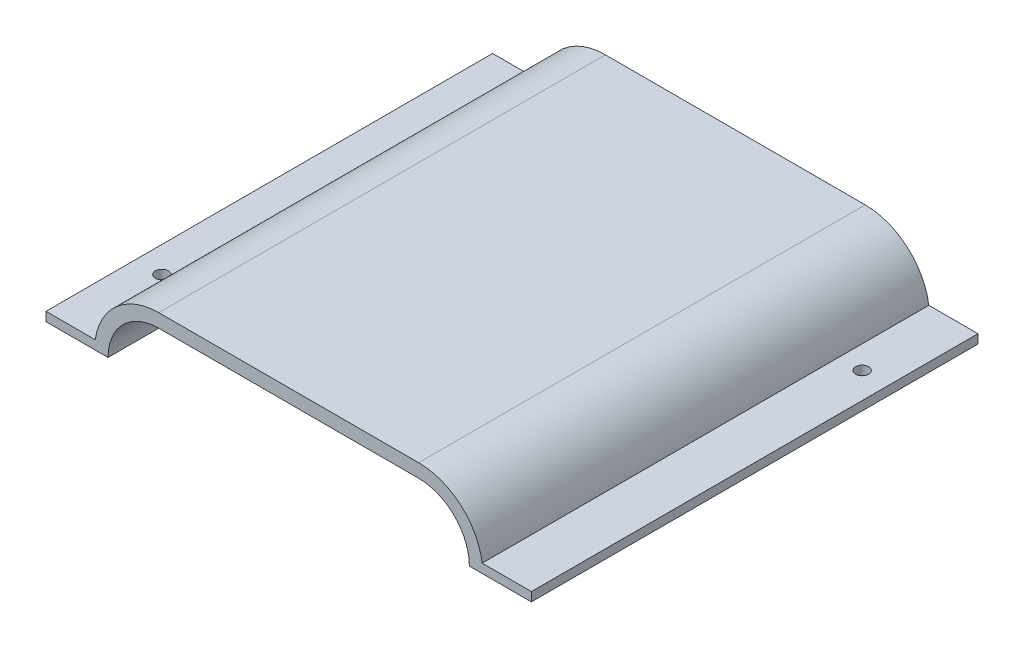
SolidWorks part; units mm, degrees
ref_plane "Front Plane" through (0, 0, 0) normal (0, 0, 1) x (1, 0, 0)
ref_plane "Top Plane" through (0, 0, 0) normal (0, 1, 0) x (1, 0, 0)
ref_plane "Right Plane" through (0, 0, 0) normal (1, 0, 0) x (0, 0, -1)
sketch "Sketch1" plane through (0, 0, 0) normal (0, 0, 1) x (1, 0, 0)
  line L0 (-28.95, 19.05) -> (28.95, 19.05) construction
  line L1 (-28.95, 30.1) -> (28.95, 30.1)
  line L2 (-28.95, 8) -> (28.95, 8)
  line L4 (0, 19.05) -> (0, 0) construction
  line L5 (-28.95, 30.35) -> (28.95, 30.35)
  line L6 (-28.95, 7.75) -> (28.95, 7.75)
  line L7 (-28.95, 33.35) -> (28.95, 33.35)
  line L8 (-28.95, 4.75) -> (28.95, 4.75)
  line L9 (-38.0268, 8) -> (38.0268, 8)
  line L10 (-43.25, 19.05) -> (43.25, 19.05)
  line L11 (-28.95, 4.75) -> (-50.25, 4.75)
  line L12 (-50.25, 4.75) -> (-50.25, 19.05)
  line L13 (-50.25, 19.05) -> (-43.25, 19.05)
  line L14 (50.25, 19.05) -> (43.25, 19.05)
  line L15 (28.95, 4.75) -> (50.25, 4.75)
  line L16 (50.25, 4.75) -> (50.25, 19.05)
  line L18 (-50.25, 19.05) -> (-54.0716, 19.05)
  line L19 (-54.0716, 19.05) -> (-54.0716, 21.05)
  line L20 (-54.0716, 21.05) -> (-40.0716, 21.05)
  line L21 (54.0716, 21.05) -> (40.0716, 21.05)
  line L22 (54.0716, 19.05) -> (54.0716, 21.05)
  line L23 (50.25, 19.05) -> (54.0716, 19.05)
  arc A0 (-28.95, 30.1) -> (-28.95, 8) centre (-28.95, 19.05) ccw
  arc A1 (28.95, 8) -> (28.95, 30.1) centre (28.95, 19.05) ccw
  arc A2 (28.95, 7.75) -> (28.95, 30.35) centre (28.95, 19.05) ccw
  arc A3 (-28.95, 30.35) -> (-28.95, 7.75) centre (-28.95, 19.05) ccw
  arc A4 (28.95, 4.75) -> (28.95, 33.35) centre (28.95, 19.05) ccw
  arc A5 (-28.95, 33.35) -> (-28.95, 4.75) centre (-28.95, 19.05) ccw
  point P2 (0, 19.05)
  point P29 (0, 19.05)
  dimension "D2" = 80
  dimension "D5" = 10
  dimension "D1" = 22.1
  dimension "D6" = 14
  dimension "D7" = 2
  dimension "D8" = 19.05
  dimension "D3" = 0.25
  dimension "D4" = 3
extrude "Boss-Extrude1" add sketch "Sketch1" along normal blind 99.5 contours L7 A5 L20 A3 L5 A2 L21 A4 | L20 A5 L10 A3 | A5 L20 L19 L18 L13 | L10 A4 L21 A2 | A4 L14 L23 L22 L21 region at (-41.6968, 20.0521, 0) region at (41.6968, 20.0521, 0) region at (-48.6373, 20.0522, 0) region at (0, 30.3818, 0) region at (48.6373, 20.0522, 0)
sketch "Sketch3" plane through (0, 19.05, 0) normal (0, -1, 0) x (1, 0, 0)
  line L2 (-54.0716, 99.5) -> (-40.25, 99.5) construction
  line L3 (40.25, 0) -> (54.0716, 0) construction
  line L5 (-40.25, 99.5) -> (-40.25, 0) construction
  line L6 (40.25, 99.5) -> (40.25, 0) construction
  circle A0 centre (-48.25, 79.5) radius 1.45
  circle A1 centre (48.25, 20) radius 1.45
  point P8 (-47.1608, 99.5)
  dimension "D1" = 8
  dimension "D2" = 2.9
  dimension "D3" = 20
  dimension "D4" = 20
  dimension "D5" = 8
extrude "Cut-Extrude1" cut sketch "Sketch3" against normal up to surface (2 mm away) up to face at (-48.5905, 21.05, 49.75)
